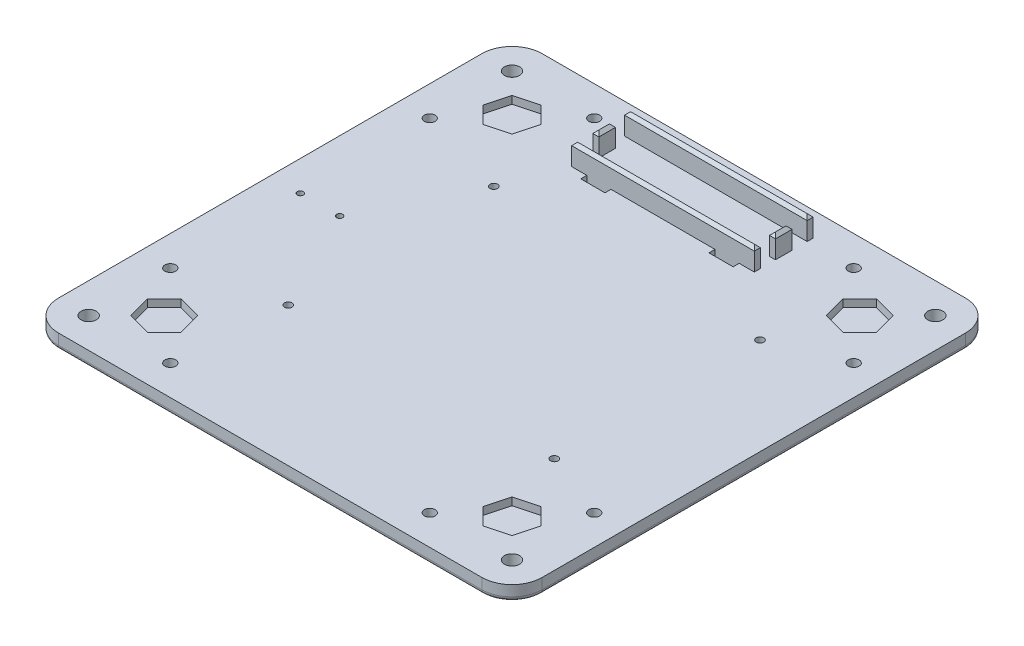
SolidWorks part; units mm, degrees
ref_plane "Front Plane" through (0, 0, 0) normal (0, 0, 1) x (1, 0, 0)
ref_plane "Top Plane" through (0, 0, 0) normal (0, 1, 0) x (1, 0, 0)
ref_plane "Right Plane" through (0, 0, 0) normal (1, 0, 0) x (0, 0, -1)
sketch "Sketch1" plane through (0, 0, 0) normal (0, 1, 0) x (1, 0, 0)
  line L1 (0, 0) -> (203.2, 0)
  line L2 (0, 0) -> (0, 203.2)
  line L3 (0, 203.2) -> (203.2, 203.2)
  line L4 (203.2, 0) -> (203.2, 203.2)
  dimension "D1" = 203.2
  dimension "D2" = 203.2
extrude "Boss-Extrude1" add sketch "Sketch1" along normal blind 6.35
fillet "Fillet1" radius 12.7 4 edges at (0, 3.175, -203.2) (0, 3.175, 0) (203.2, 3.175, 0) (203.2, 3.175, -203.2)
sketch "Sketch2" plane through (0, 0, 0) normal (0, -1, 0) x (1, 0, 0)
  circle A0 centre (12.7, -12.7) radius 3.175
  circle A1 centre (190.5, -12.7) radius 3.175
  circle A2 centre (190.5, -190.5) radius 3.175
  circle A3 centre (12.7, -190.5) radius 3.175
  arc A4 (190.5, -203.2) -> (203.2, -190.5) centre (190.5, -190.5) ccw construction
  arc A5 (12.7, 0) -> (0, -12.7) centre (12.7, -12.7) ccw construction
  dimension "D1" = 6.35
extrude "Cut-Extrude1" cut sketch "Sketch2" against normal through all
sketch "Sketch22" plane through (0, 6.35, 0) normal (0, 1, 0) x (1, 0, 0)
  line L17 (190.5, 203.2) -> (12.7, 203.2) construction
  line L18 (203.2, 12.7) -> (203.2, 190.5) construction
  line L21 (181.6542, 181.6542) -> (172.0521, 184.2271)
  line L22 (172.0521, 184.2271) -> (165.0229, 177.1979)
  line L23 (165.0229, 177.1979) -> (167.5958, 167.5958)
  line L24 (167.5958, 167.5958) -> (177.1979, 165.0229)
  line L25 (177.1979, 165.0229) -> (184.2271, 172.0521)
  line L26 (184.2271, 172.0521) -> (181.6542, 181.6542)
  line L27 (174.625, 174.625) -> (190.5, 190.5) construction
  line L28 (101.6, 203.2) -> (101.6, 0) construction
  line L29 (12.7, 0) -> (190.5, 0) construction
  line L30 (203.2, 101.6) -> (0, 101.6) construction
  line L31 (0, 190.5) -> (0, 12.7) construction
  line L32 (28.575, 174.625) -> (12.7, 190.5) construction
  line L33 (18.9729, 172.0521) -> (21.5458, 181.6542)
  line L34 (26.0021, 165.0229) -> (18.9729, 172.0521)
  line L35 (35.6042, 167.5958) -> (26.0021, 165.0229)
  line L36 (38.1771, 177.1979) -> (35.6042, 167.5958)
  line L37 (31.1479, 184.2271) -> (38.1771, 177.1979)
  line L38 (21.5458, 181.6542) -> (31.1479, 184.2271)
  line L39 (174.625, 28.575) -> (190.5, 12.7) construction
  line L40 (184.2271, 31.1479) -> (181.6542, 21.5458)
  line L41 (177.1979, 38.1771) -> (184.2271, 31.1479)
  line L42 (167.5958, 35.6042) -> (177.1979, 38.1771)
  line L43 (165.0229, 26.0021) -> (167.5958, 35.6042)
  line L44 (172.0521, 18.9729) -> (165.0229, 26.0021)
  line L45 (181.6542, 21.5458) -> (172.0521, 18.9729)
  line L46 (28.575, 28.575) -> (12.7, 12.7) construction
  line L47 (21.5458, 21.5458) -> (31.1479, 18.9729)
  line L48 (31.1479, 18.9729) -> (38.1771, 26.0021)
  line L49 (38.1771, 26.0021) -> (35.6042, 35.6042)
  line L50 (35.6042, 35.6042) -> (26.0021, 38.1771)
  line L51 (26.0021, 38.1771) -> (18.9729, 31.1479)
  line L52 (18.9729, 31.1479) -> (21.5458, 21.5458)
  circle A0 centre (174.625, 174.625) radius 8.609 construction
  circle A1 centre (28.575, 174.625) radius 8.609 construction
  circle A2 centre (174.625, 28.575) radius 8.609 construction
  circle A3 centre (28.575, 28.575) radius 8.609 construction
  dimension "D5" = 17.218
  dimension "D3" = 28.575
  dimension "D4" = 28.575
extrude "Cut-Extrude2" cut sketch "Sketch22" against normal blind 3.175
fillet "Fillet2" radius 1.905 12 edges at (3.7197, 0, -3.7197) (101.6, 0, 0) (199.4803, 0, -3.7197) (203.2, 0, -101.6) (199.4803, 0, -199.4803) (101.6, 0, -203.2) (3.7197, 0, -199.4803) (0, 0, -101.6) (12.7, 0, -15.875) (190.5, 0, -15.875) (190.5, 0, -193.675) (12.7, 0, -193.675)
sketch "Sketch28" plane through (0, 6.35, 0) normal (0, 1, 0) x (1, 0, 0)
  line L0 (190.5, 203.2) -> (12.7, 203.2) construction
  line L1 (203.2, 12.7) -> (203.2, 190.5) construction
  line L2 (12.7, 0) -> (190.5, 0) construction
  line L4 (0, 190.5) -> (0, 12.7) construction
  circle A0 centre (47.117, 190.627) radius 2.286
  circle A1 centre (156.083, 190.627) radius 2.286
  circle A2 centre (190.627, 156.083) radius 2.286
  circle A3 centre (190.627, 47.117) radius 2.286
  circle A4 centre (156.083, 12.573) radius 2.286
  circle A5 centre (47.117, 12.573) radius 2.286
  circle A6 centre (12.573, 156.083) radius 2.286
  circle A7 centre (12.573, 47.117) radius 2.286
  dimension "D4" = 4.572
  dimension "D1" = 12.573
  dimension "D2" = 12.573
  dimension "D3" = 12.573
  dimension "D5" = 12.573
  dimension "D6" = 47.117
  dimension "D7" = 47.117
  dimension "D8" = 47.117
  dimension "D9" = 47.117
extrude "Cut-Extrude3" cut sketch "Sketch28" against normal through all
sketch "Sketch29" plane through (0, 6.35, 0) normal (0, 1, 0) x (1, 0, 0)
  line L0 (43.18, 152.4) -> (43.18, 50.8) construction
  line L1 (43.18, 50.8) -> (170.18, 50.8) construction
  line L2 (170.18, 50.8) -> (170.18, 152.4) construction
  line L3 (170.18, 152.4) -> (43.18, 152.4) construction
  line L6 (203.2, 12.7) -> (203.2, 190.5) construction
  line L20 (0, 190.5) -> (0, 12.7) construction
  point P2 (170.18, 101.6)
  point P7 (203.2, 101.6)
  dimension "D1" = 127
  dimension "D2" = 101.6
  dimension "D8" = 43.18
sketch "Sketch30" plane through (0, 6.35, 0) normal (0, 1, 0) x (1, 0, 0)
  line L0 (43.18, 152.4) -> (170.18, 152.4) construction
  line L1 (170.18, 152.4) -> (170.18, 50.8) construction
  line L2 (170.18, 50.8) -> (43.18, 50.8) construction
  line L3 (43.18, 50.8) -> (43.18, 152.4) construction
  circle A0 centre (50.8, 144.78) radius 1.5875
  circle A1 centre (162.56, 144.78) radius 1.5875
  circle A2 centre (162.56, 58.42) radius 1.5875
  circle A3 centre (50.8, 58.42) radius 1.5875
  dimension "D1" = 3.175
  dimension "D2" = 7.62
  dimension "D3" = 7.62
  dimension "D4" = 7.62
  dimension "D5" = 7.62
  dimension "D6" = 127
  dimension "D7" = 101.6
extrude "Cut-Extrude4" cut sketch "Sketch30" against normal through all
sketch "Sketch31" plane through (0, 6.35, 0) normal (0, 1, 0) x (1, 0, 0)
  line L0 (10.16, 104.14) -> (10.16, 76.2) construction
  line L1 (10.16, 76.2) -> (31.75, 76.2) construction
  line L2 (31.75, 76.2) -> (31.75, 104.14) construction
  line L3 (31.75, 104.14) -> (10.16, 104.14) construction
  line L4 (0, 190.5) -> (0, 12.7) construction
  line L5 (12.7, 0) -> (190.5, 0) construction
  line L6 (12.7, 101.6) -> (29.21, 101.6) construction
  circle A0 centre (12.7, 101.6) radius 1.27
  circle A1 centre (29.21, 101.6) radius 1.27
  point P12 (20.955, 101.6)
  point P13 (20.955, 104.14)
  dimension "D5" = 16.51
  dimension "D7" = 2.54
  dimension "D1" = 27.94
  dimension "D2" = 21.59
  dimension "D3" = 10.16
  dimension "D4" = 76.2
  dimension "D6" = 2.54
extrude "Cut-Extrude5" cut sketch "Sketch31" against normal through all
sketch "Sketch32" plane through (0, 6.35, 0) normal (0, 1, 0) x (1, 0, 0)
  line L0 (0, 190.5) -> (0, 12.7) construction
  line L1 (62.5069, 190.5) -> (134.1349, 190.5)
  line L2 (62.5069, 184.15) -> (62.5069, 177.1904)
  line L3 (62.5069, 170.8404) -> (134.1349, 170.8404)
  line L6 (190.5, 203.2) -> (12.7, 203.2) construction
  line L7 (59.9669, 193.04) -> (136.6749, 193.04)
  line L8 (136.6749, 193.04) -> (136.6749, 190.5)
  line L9 (59.9669, 168.3004) -> (136.6749, 168.3004)
  line L10 (59.9669, 193.04) -> (59.9669, 190.5)
  line L11 (62.5069, 190.5) -> (59.9669, 190.5)
  line L12 (62.5069, 184.15) -> (59.9669, 184.15)
  line L13 (62.5069, 190.5) -> (62.5069, 170.8404) construction
  line L14 (59.9669, 184.15) -> (59.9669, 177.1904)
  line L15 (59.9669, 193.04) -> (59.9669, 168.3004) construction
  line L16 (62.5069, 177.1904) -> (59.9669, 177.1904)
  line L17 (134.1349, 170.8404) -> (136.6749, 170.8404)
  line L22 (134.1349, 190.5) -> (136.6749, 190.5)
  line L23 (134.1349, 190.5) -> (134.1349, 170.8404) construction
  line L25 (136.6749, 193.04) -> (136.6749, 168.3004) construction
  line L26 (136.6749, 170.8404) -> (136.6749, 168.3004)
  line L27 (59.9669, 170.8404) -> (59.9669, 168.3004)
  line L28 (62.5069, 170.8404) -> (59.9669, 170.8404)
  line L30 (136.6749, 184.15) -> (134.1349, 184.15)
  line L31 (136.6749, 184.15) -> (136.6749, 177.1904)
  line L32 (136.6749, 177.1904) -> (134.1349, 177.1904)
  line L33 (134.1349, 184.15) -> (134.1349, 177.1904)
  point P21 (61.2369, 177.1904)
  dimension "D1" = 19.6596
  dimension "D2" = 71.628
  dimension "D3" = 62.5069
  dimension "D4" = 12.7
  dimension "D6" = 6.35
  dimension "D7" = 6.35
  dimension "D8" = 6.35
  dimension "D9" = 6.35
  dimension "D10" = 2.54
  dimension "D11" = 2.54
  dimension "D5" = 2.54
extrude "Boss-Extrude3" add sketch "Sketch32" along normal blind 8.89
chamfer "Chamfer2" distance 1.27 angle 45 16 edges at (59.9669, 15.24, -191.77) (98.3209, 15.24, -193.04) (136.6749, 15.24, -191.77) (98.3209, 15.24, -190.5) (136.6749, 15.24, -169.5704) (98.3209, 15.24, -168.3004) (59.9669, 15.24, -169.5704) (98.3209, 15.24, -170.8404) (135.4049, 15.24, -177.1904) (134.1349, 15.24, -180.6702) (135.4049, 15.24, -184.15) (136.6749, 15.24, -180.6702) (62.5069, 15.24, -180.6702) (61.2369, 15.24, -177.1904) (59.9669, 15.24, -180.6702) (61.2369, 15.24, -184.15)
sketch "Sketch33" plane through (0, 6.35, 0) normal (0, 1, 0) x (1, 0, 0)
  line L0 (136.6749, 168.3004) -> (59.9669, 168.3004) construction
  line L1 (66.3169, 168.3004) -> (76.4769, 168.3004)
  line L2 (66.3169, 168.3004) -> (66.3169, 165.7604)
  line L3 (66.3169, 165.7604) -> (76.4769, 165.7604)
  line L4 (76.4769, 168.3004) -> (76.4769, 165.7604)
  line L5 (136.6749, 193.04) -> (59.9669, 193.04) construction
  line L6 (120.1649, 168.3004) -> (130.3249, 168.3004)
  line L7 (120.1649, 168.3004) -> (120.1649, 165.7604)
  line L8 (120.1649, 165.7604) -> (130.3249, 165.7604)
  line L9 (130.3249, 168.3004) -> (130.3249, 165.7604)
  line L10 (130.3249, 193.04) -> (120.1649, 193.04)
  line L11 (130.3249, 193.04) -> (130.3249, 195.58)
  line L12 (130.3249, 195.58) -> (120.1649, 195.58)
  line L13 (120.1649, 193.04) -> (120.1649, 195.58)
  line L15 (66.3169, 193.04) -> (76.4769, 193.04)
  line L16 (66.3169, 193.04) -> (66.3169, 195.58)
  line L17 (66.3169, 195.58) -> (76.4769, 195.58)
  line L18 (76.4769, 193.04) -> (76.4769, 195.58)
  line L19 (59.9669, 170.8404) -> (59.9669, 168.3004) construction
  line L20 (59.9669, 190.5) -> (59.9669, 193.04) construction
  line L21 (136.6749, 168.3004) -> (136.6749, 170.8404) construction
  line L22 (136.6749, 193.04) -> (136.6749, 190.5) construction
  dimension "D1" = 2.54
  dimension "D2" = 10.16
  dimension "D3" = 6.35
  dimension "D4" = 6.35
  dimension "D5" = 6.35
  dimension "D6" = 6.35
extrude "Cut-Extrude6" cut sketch "Sketch33" against normal through all
